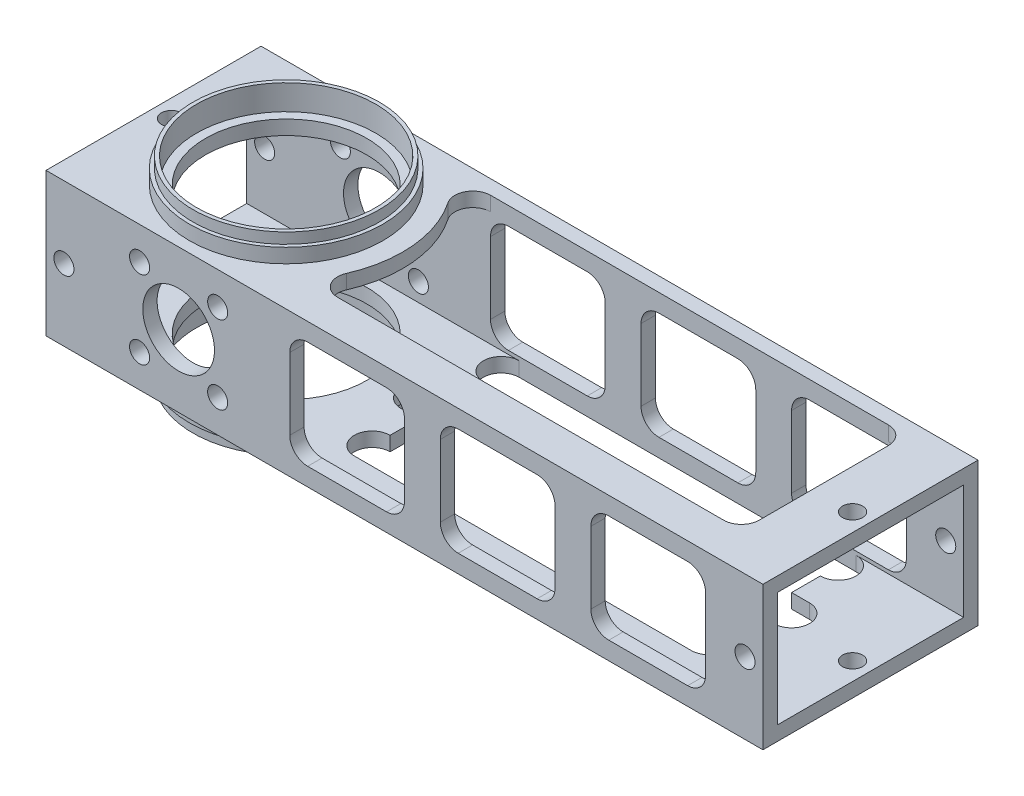
SolidWorks part; units mm, degrees
material "6061 Alloy"
ref_plane "Front Plane" through (0, 0, 0) normal (0, 0, 1) x (1, 0, 0)
ref_plane "Top Plane" through (0, 0, 0) normal (0, 1, 0) x (1, 0, 0)
ref_plane "Right Plane" through (0, 0, 0) normal (1, 0, 0) x (0, 0, -1)
sketch "Sketch1" plane through (0, 0, 0) normal (1, 0, 0) x (0, 0, -1)
  line L0 (2.54, 22.86) -> (35.56, 22.86)
  line L1 (0, 0) -> (38.1, 0)
  line L2 (0, 0) -> (0, 25.4)
  line L3 (0, 25.4) -> (38.1, 25.4)
  line L4 (38.1, 0) -> (38.1, 25.4)
  line L5 (35.56, 2.54) -> (35.56, 22.86)
  line L6 (2.54, 2.54) -> (35.56, 2.54)
  line L7 (2.54, 2.54) -> (2.54, 22.86)
  dimension "D1" = 38.1
  dimension "D2" = 25.4
  dimension "D3" = 33.02
extrude "Boss-Extrude1" add sketch "Sketch1" along normal blind 127
sketch "Sketch2" plane through (0, 25.4, 0) normal (0, 1, 0) x (1, 0, 0)
  line L0 (0, 19.05) -> (23.495, 19.05) construction
  line L1 (0, 38.1) -> (0, 0) construction
  circle A0 centre (23.495, 19.05) radius 14.2875
  dimension "D2" = 28.575
  dimension "D1" = 23.495
extrude "Cut-Extrude1" cut sketch "Sketch2" against normal through all
sketch "Sketch3" plane through (0, 0, 0) normal (0, 0, 1) x (1, 0, 0)
  line L0 (0, 12.7) -> (23.495, 12.7) construction
  line L1 (0, 25.4) -> (0, 0) construction
  line L2 (0, 25.4) -> (23.495, 25.4) construction
  line L3 (63.5, 22.225) -> (69.85, 22.225) construction
  line L4 (16.5802, 5.7852) -> (30.4098, 5.7852) construction
  line L5 (16.5802, 5.7852) -> (16.5802, 19.6148) construction
  line L6 (16.5802, 19.6148) -> (30.4098, 19.6148) construction
  line L7 (30.4098, 5.7852) -> (30.4098, 19.6148) construction
  line L8 (16.5802, 5.7852) -> (30.4098, 19.6148) construction
  line L9 (16.5802, 19.6148) -> (30.4098, 5.7852) construction
  line L10 (46.355, 22.225) -> (60.325, 22.225)
  line L11 (43.18, 19.05) -> (43.18, 6.35)
  line L12 (46.355, 3.175) -> (60.325, 3.175)
  line L13 (63.5, 19.05) -> (63.5, 6.35)
  line L14 (73.025, 22.225) -> (86.995, 22.225)
  line L15 (69.85, 19.05) -> (69.85, 6.35)
  line L16 (73.025, 3.175) -> (86.995, 3.175)
  line L17 (90.17, 19.05) -> (90.17, 6.35)
  line L18 (99.695, 22.225) -> (113.665, 22.225)
  line L19 (96.52, 19.05) -> (96.52, 6.35)
  line L20 (99.695, 3.175) -> (113.665, 3.175)
  line L21 (116.84, 19.05) -> (116.84, 6.35)
  line L22 (90.17, 22.225) -> (96.52, 22.225) construction
  line L23 (127, 12.7) -> (116.84, 12.7) construction
  line L24 (127, 25.4) -> (127, 0) construction
  circle A0 centre (23.495, 12.7) radius 6.35
  circle A1 centre (16.5802, 19.6148) radius 1.778
  circle A2 centre (16.5802, 5.7852) radius 1.778
  circle A3 centre (30.4098, 5.7852) radius 1.778
  circle A4 centre (30.4098, 19.6148) radius 1.778
  arc A5 (113.665, 22.225) -> (116.84, 19.05) centre (113.665, 19.05) cw
  arc A6 (113.665, 3.175) -> (116.84, 6.35) centre (113.665, 6.35) ccw
  arc A7 (96.52, 6.35) -> (99.695, 3.175) centre (99.695, 6.35) ccw
  arc A8 (99.695, 22.225) -> (96.52, 19.05) centre (99.695, 19.05) ccw
  arc A9 (86.995, 22.225) -> (90.17, 19.05) centre (86.995, 19.05) cw
  arc A10 (86.995, 3.175) -> (90.17, 6.35) centre (86.995, 6.35) ccw
  arc A11 (69.85, 6.35) -> (73.025, 3.175) centre (73.025, 6.35) ccw
  arc A12 (73.025, 22.225) -> (69.85, 19.05) centre (73.025, 19.05) ccw
  arc A13 (60.325, 22.225) -> (63.5, 19.05) centre (60.325, 19.05) cw
  arc A14 (60.325, 3.175) -> (63.5, 6.35) centre (60.325, 6.35) ccw
  arc A15 (43.18, 6.35) -> (46.355, 3.175) centre (46.355, 6.35) ccw
  arc A16 (46.355, 22.225) -> (43.18, 19.05) centre (46.355, 19.05) ccw
  point P33 (116.84, 22.225)
  point P36 (116.84, 3.175)
  dimension "D1" = 12.7
  dimension "D3" = 3.556
  dimension "D8" = 3.175
  dimension "D2" = 19.558
  dimension "D4" = 20.32
  dimension "D5" = 19.05
  dimension "D6" = 6.35
  dimension "D7" = 10.16
extrude "Cut-Extrude2" cut sketch "Sketch3" against normal through all
sketch "Sketch4" plane through (0, 25.4, 0) normal (0, 1, 0) x (1, 0, 0)
  line L0 (45.3195, 6.35) -> (113.665, 6.35)
  line L1 (116.84, 9.525) -> (116.84, 32.385)
  line L2 (113.665, 35.56) -> (43.2235, 35.56)
  line L3 (116.84, 19.05) -> (127, 19.05) construction
  line L4 (127, 38.1) -> (127, 0) construction
  line L5 (127, 0) -> (116.84, 0) construction
  line L6 (127, 38.1) -> (0, 38.1) construction
  line L7 (127, 0) -> (0, 0) construction
  line L8 (79.4923, 6.35) -> (79.4923, 35.56) construction
  arc A0 (42.4096, 10.795) -> (40.593, 30.607) centre (23.495, 19.05) ccw
  circle A1 centre (23.495, 19.05) radius 14.2875 construction
  arc A2 (113.665, 6.35) -> (116.84, 9.525) centre (113.665, 9.525) ccw
  arc A3 (116.84, 32.385) -> (113.665, 35.56) centre (113.665, 32.385) ccw
  arc A4 (40.593, 30.607) -> (43.2235, 35.56) centre (43.2235, 32.385) cw
  arc A5 (42.4096, 10.795) -> (45.3195, 6.35) centre (45.3195, 9.525) ccw
  dimension "D3" = 6.35
  dimension "D4" = 3.175
  dimension "D1" = 2.54
  dimension "D2" = 6.35
extrude "Cut-Extrude3" cut sketch "Sketch4" against normal up to next
hole_wizard "#4 (0.209) Diameter Hole1" positions "3DSketch1" profile "Sketch5" hole size "#4" standard "ANSI Inch" end condition up to next
sketch3d "3DSketch1"
  line L0 (127, 25.4, -19.05) -> (123.825, 25.4, -19.05) construction
  line L1 (127, 25.4, -38.1) -> (127, 25.4, 0) construction
  line L6 (127, 12.7, 0) -> (123.825, 12.7, 0) construction
  line L7 (127, 25.4, 0) -> (127, 0, 0) construction
  line L13 (0, 25.4, -19.05) -> (3.175, 25.4, -19.05) construction
  line L14 (0, 25.4, -38.1) -> (0, 25.4, 0) construction
  line L17 (0, 12.7, 0) -> (3.175, 12.7, 0) construction
  line L18 (0, 25.4, 0) -> (0, 0, 0) construction
  point P13 (123.825, 12.7, 0)
  point P24 (3.175, 25.4, -19.05)
  point P30 (3.175, 12.7, 0)
  point P48 (3.175, 25.4, -19.05)
  point P67 (3.175, 25.4, -19.05)
  point P69 (3.175, 12.7, 0)
  point P77 (123.825, 25.4, -19.05)
  point P79 (123.825, 12.7, 0)
  point P81 (123.825, 0, -19.05)
  point P83 (123.825, 12.7, -38.1)
  point P90 (3.175, 12.7, -38.1)
  point P92 (3.175, 0, -19.05)
  dimension "D1" = 3.175
sketch "Sketch5" plane through (3.175, 25.4, -19.05) normal (1, 0, 0) x (0, 0, 1)
  line L0 (0, 0) -> (0, 2.541)
  line L1 (0, 2.541) -> (1.778, 2.541)
  line L2 (1.778, 2.541) -> (1.778, 0)
  line L5 (1.778, 0) -> (0, 0)
  line L11 (0, -6.35) -> (0, 107.95) construction
  dimension "Thru Hole Dia." = 3.556
  dimension "Thru Hole Depth" = 2.541
sketch "Sketch6" plane through (0, 0, 0) normal (0, -1, 0) x (1, 0, 0)
  line L0 (48.26, -35.56) -> (107.95, -35.56)
  line L1 (48.26, -6.35) -> (107.95, -6.35)
  line L2 (79.4923, -6.35) -> (79.4923, -35.56) construction
  line L3 (113.665, -35.56) -> (43.2235, -35.56) construction
  line L4 (127, 0) -> (127, -38.1) construction
  line L5 (48.26, -6.35) -> (48.26, -35.56) construction
  line L6 (107.95, -6.35) -> (107.95, -35.56) construction
  line L8 (107.95, -12.7) -> (107.95, -17.78)
  line L9 (107.95, -17.78) -> (111.125, -17.78)
  line L10 (107.95, -29.21) -> (107.95, -24.13)
  line L11 (107.95, -24.13) -> (111.125, -24.13)
  line L12 (48.26, -29.21) -> (48.26, -24.13)
  line L13 (48.26, -12.7) -> (48.26, -17.78)
  line L14 (48.26, -17.78) -> (45.085, -17.78)
  line L15 (48.26, -24.13) -> (45.085, -24.13)
  arc A0 (107.95, -6.35) -> (107.95, -12.7) centre (107.95, -9.525) cw
  arc A1 (107.95, -35.56) -> (107.95, -29.21) centre (107.95, -32.385) ccw
  arc A2 (48.26, -35.56) -> (48.26, -29.21) centre (48.26, -32.385) cw
  arc A3 (48.26, -6.35) -> (48.26, -12.7) centre (48.26, -9.525) ccw
  arc A5 (111.125, -17.78) -> (111.125, -24.13) centre (111.125, -20.955) cw
  arc A6 (45.085, -17.78) -> (45.085, -24.13) centre (45.085, -20.955) ccw
  dimension "D1" = 59.69
  dimension "D2" = 3.175
  dimension "D3" = 3.175
  dimension "D4" = 19.05
extrude "Cut-Extrude4" cut sketch "Sketch6" against normal up to next
ref_plane "Plane1" through (0, 0, -19.05) normal (0, 0, 1) x (1, 0, 0)
sketch "Sketch7" plane through (0, 0, -19.05) normal (0, 0, 1) x (1, 0, 0)
  line L0 (23.495, -4.445) -> (23.495, 29.845) construction
  line L1 (39.37, 29.845) -> (39.37, 25.4)
  line L2 (39.37, 25.4) -> (40.64, 25.4)
  line L3 (40.64, 25.4) -> (40.64, 27.94)
  line L4 (40.64, 27.94) -> (40.005, 27.94)
  line L5 (40.005, 27.94) -> (40.005, 29.845)
  line L6 (40.005, 29.845) -> (39.37, 29.845)
  line L7 (39.37, -4.445) -> (39.37, 0)
  line L12 (39.37, 0) -> (40.64, 0)
  line L13 (40.64, 0) -> (40.64, -2.54)
  line L14 (40.64, -2.54) -> (40.005, -2.54)
  line L15 (40.005, -2.54) -> (40.005, -4.445)
  line L16 (40.005, -4.445) -> (39.37, -4.445)
  line L17 (127, 25.4) -> (0, 25.4) construction
  dimension "D1" = 34.29
  dimension "D2" = 31.75
  dimension "D3" = 33.02
  dimension "D4" = 4.445
  dimension "D5" = 2.54
revolve "Revolve1" add sketch "Sketch7" angle 360 about L0
